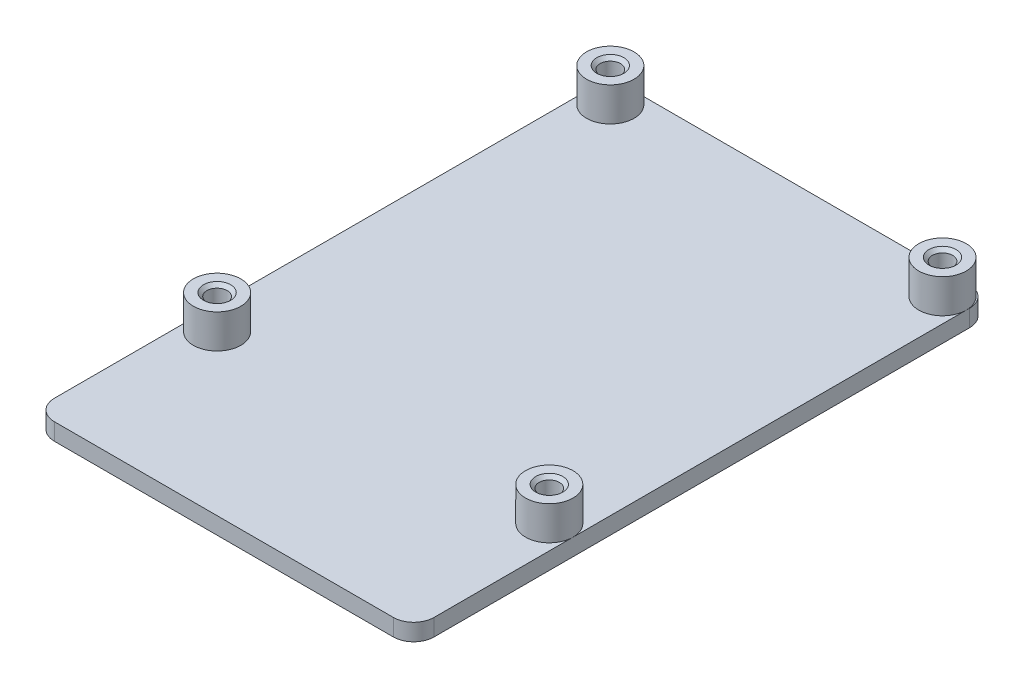
SolidWorks part; units mm, degrees
material "6061-T6 (SS)"
ref_plane "Front Plane" through (0, 0, 0) normal (0, 0, 1) x (1, 0, 0)
ref_plane "Top Plane" through (0, 0, 0) normal (0, 1, 0) x (1, 0, 0)
ref_plane "Right Plane" through (0, 0, 0) normal (1, 0, 0) x (0, 0, -1)
ref_axis "Axis1" through (0, 0, 55) along (0, 0, -1)
sketch "Sketch1" plane through (0, 0, 0) normal (0, 1, 0) x (1, 0, 0)
  line L0 (-125, 0) -> (0, 0) construction
  line L1 (125, 0) -> (125, 125) construction
  line L2 (125, 125) -> (-125, 125) construction
  line L3 (-125, 125) -> (-125, 0) construction
  line L4 (41.25, 3.75) -> (41.25, 1.5) construction
  line L5 (39, 101.5) -> (109, 101.5)
  line L6 (39, 101.5) -> (39, 1.5)
  line L7 (39, 1.5) -> (109, 1.5)
  line L8 (109, 101.5) -> (109, 1.5)
  line L9 (39, 101.5) -> (109, 1.5) construction
  line L10 (39, 1.5) -> (109, 101.5) construction
  line L11 (41.25, 3.75) -> (39, 3.75) construction
  line L12 (-114.29, 77.51) -> (-116.54, 77.51) construction
  line L13 (78.2, 11.5) -> (87.2, 11.5)
  line L14 (78.2, 11.5) -> (78.2, 1.5)
  line L15 (78.2, 1.5) -> (87.2, 1.5)
  line L16 (87.2, 11.5) -> (87.2, 1.5)
  line L17 (78.2, 11.5) -> (87.2, 1.5) construction
  line L18 (78.2, 1.5) -> (87.2, 11.5) construction
  line L19 (90.5, 16.5) -> (106.5, 16.5)
  line L20 (90.5, 16.5) -> (90.5, 1.5)
  line L21 (90.5, 1.5) -> (106.5, 1.5)
  line L22 (106.5, 16.5) -> (106.5, 1.5)
  line L23 (90.5, 16.5) -> (106.5, 1.5) construction
  line L24 (90.5, 1.5) -> (106.5, 16.5) construction
  line L25 (-116.54, 113.59) -> (-93.46, 113.59)
  line L26 (-116.54, 113.59) -> (-116.54, 71.41)
  line L27 (-116.54, 71.41) -> (-93.46, 71.41)
  line L28 (-93.46, 113.59) -> (-93.46, 71.41)
  line L29 (-116.54, 113.59) -> (-93.46, 71.41) construction
  line L30 (-116.54, 71.41) -> (-93.46, 113.59) construction
  line L31 (-114.29, 77.51) -> (-114.29, 71.41) construction
  line L32 (-95.71, 107.49) -> (-95.71, 113.59) construction
  line L33 (-95.71, 107.49) -> (-93.46, 107.49) construction
  line L34 (-64.5, 85.45) -> (-68, 85.45) construction
  line L35 (-65, 88.95) -> (-15, 88.95)
  line L36 (-68, 85.95) -> (-68, 6.95)
  line L37 (-65, 3.95) -> (-15, 3.95)
  line L38 (-12, 85.95) -> (-12, 6.95)
  line L39 (-68, 88.95) -> (-12, 3.95) construction
  line L40 (-68, 3.95) -> (-12, 88.95) construction
  line L41 (-64.5, 85.45) -> (-15.5, 85.45) construction
  line L42 (-64.5, 85.45) -> (-64.5, 27.45) construction
  line L43 (-64.5, 27.45) -> (-15.5, 27.45) construction
  line L44 (-15.5, 85.45) -> (-15.5, 27.45) construction
  line L45 (0, 0) -> (0, 125) construction
  line L46 (0, 0) -> (125, 0) construction
  line L47 (-64.5, 85.45) -> (-64.5, 88.95) construction
  line L48 (74, 0) -> (74, 125) construction
  line L49 (-65.69, 22.9) -> (-49.81, 22.9)
  line L50 (-65.69, 22.9) -> (-65.69, 1.5)
  line L51 (-65.69, 1.5) -> (-49.81, 1.5)
  line L52 (-49.81, 22.9) -> (-49.81, 1.5)
  line L53 (-65.69, 22.9) -> (-49.81, 1.5) construction
  line L54 (-65.69, 1.5) -> (-49.81, 22.9) construction
  line L55 (-45.65, 19.42) -> (-32.35, 19.42)
  line L56 (-45.65, 19.42) -> (-45.65, 1.5)
  line L57 (-45.65, 1.5) -> (-32.35, 1.5)
  line L58 (-32.35, 19.42) -> (-32.35, 1.5)
  line L59 (-45.65, 19.42) -> (-32.35, 1.5) construction
  line L60 (-45.65, 1.5) -> (-32.35, 19.42) construction
  line L61 (-27.65, 19.42) -> (-14.35, 19.42)
  line L62 (-27.65, 19.42) -> (-27.65, 1.5)
  line L63 (-27.65, 1.5) -> (-14.35, 1.5)
  line L64 (-14.35, 19.42) -> (-14.35, 1.5)
  line L65 (-27.65, 19.42) -> (-14.35, 1.5) construction
  line L66 (-27.65, 1.5) -> (-14.35, 19.42) construction
  line L67 (-40, 0) -> (-40, 125) construction
  line L68 (-114.29, 11.41) -> (-114.29, 17.51) construction
  line L69 (-116.54, 53.59) -> (-93.46, 53.59)
  line L70 (-116.54, 53.59) -> (-116.54, 11.41)
  line L71 (-116.54, 11.41) -> (-93.46, 11.41)
  line L72 (-93.46, 53.59) -> (-93.46, 11.41)
  line L73 (-116.54, 53.59) -> (-93.46, 11.41) construction
  line L74 (-116.54, 11.41) -> (-93.46, 53.59) construction
  line L75 (-114.29, 17.51) -> (-116.54, 17.51) construction
  line L76 (-95.71, 53.59) -> (-95.71, 47.49) construction
  line L77 (-95.71, 47.49) -> (-93.46, 47.49) construction
  line L78 (-105, 0) -> (-105, 32.5) construction
  line L79 (-105, 32.5) -> (-105, 92.5) construction
  line L80 (-105, 92.5) -> (-105, 125) construction
  line L81 (-64.5, 27.45) -> (-15.5, 85.45) construction
  line L82 (-15.5, 27.45) -> (-64.5, 85.45) construction
  circle A0 centre (106, 81.5) radius 1.75
  circle A1 centre (106, 19.5) radius 1.75
  circle A2 centre (71.1, 99.7) radius 1.75
  circle A3 centre (68.3, 67.9) radius 1.75
  circle A4 centre (41.25, 3.75) radius 1.75
  circle A5 centre (-95.71, 107.49) radius 1.4
  circle A6 centre (-114.29, 77.51) radius 1.4
  arc A7 (-15, 3.95) -> (-12, 6.95) centre (-15, 6.95) ccw
  arc A8 (-68, 6.95) -> (-65, 3.95) centre (-65, 6.95) ccw
  arc A9 (-15, 88.95) -> (-12, 85.95) centre (-15, 85.95) cw
  arc A10 (-65, 88.95) -> (-68, 85.95) centre (-65, 85.95) ccw
  circle A11 centre (-64.5, 85.45) radius 1.375
  circle A12 centre (-15.5, 85.45) radius 1.375
  circle A13 centre (-64.5, 27.45) radius 1.375
  circle A14 centre (-15.5, 27.45) radius 1.375
  circle A15 centre (-95.71, 47.49) radius 1.4
  circle A16 centre (-114.29, 17.51) radius 1.4
  circle A17 centre (41.25, 3.75) radius 2.84
  point P0 (74, 51.5)
  point P3 (-105, 92.5)
  point P4 (0, 0)
  point P24 (82.7, 6.5)
  point P30 (98.5, 9)
  point P47 (-40, 46.45)
  point P65 (-39, 10.46)
  point P69 (-57.75, 12.2)
  point P84 (-21, 10.46)
  point P89 (-105, 32.5)
  point P111 (-40, 56.45)
  dimension "D5" = 3.5
  dimension "D26" = 3
  dimension "D27" = 2.75
  dimension "D44" = 2.8
  dimension "D49" = 5.68
  dimension "D1" = 250
  dimension "D2" = 125
  dimension "D3" = 100
  dimension "D4" = 70
  dimension "D6" = 20
  dimension "D7" = 3
  dimension "D8" = 82
  dimension "D9" = 1.8
  dimension "D10" = 37.9
  dimension "D11" = 33.6
  dimension "D12" = 40.7
  dimension "D13" = 2.25
  dimension "D14" = 9
  dimension "D15" = 10
  dimension "D16" = 26.3
  dimension "D17" = 16
  dimension "D18" = 15
  dimension "D19" = 10.5
  dimension "D20" = 23.08
  dimension "D21" = 42.18
  dimension "D22" = 6.1
  dimension "D23" = 2.25
  dimension "D24" = 85
  dimension "D25" = 56
  dimension "D28" = 58
  dimension "D29" = 49
  dimension "D30" = 10.25
  dimension "D31" = 29
  dimension "D32" = 47
  dimension "D33" = 21.4
  dimension "D34" = 15.88
  dimension "D35" = 2.45
  dimension "D36" = 13.3
  dimension "D37" = 17.92
  dimension "D38" = 2.45
  dimension "D39" = 2.45
  dimension "D40" = 2.25
  dimension "D41" = 1.5
  dimension "D42" = 40
  dimension "D43" = 1.5
  dimension "D45" = 60
  dimension "D46" = 3.5
  dimension "D47" = 20
  dimension "D48" = 16
sketch "Sketch2" plane through (0, 0, 0) normal (0, 1, 0) x (1, 0, 0)
  line L0 (-68, 85.95) -> (-68, 6.95) construction
  line L1 (-65, 3.95) -> (-15, 3.95) construction
  line L2 (-12, 85.95) -> (-12, 6.95) construction
  line L3 (-65, 88.95) -> (-15, 88.95) construction
  line L4 (-68, 85.95) -> (-68, 6.95)
  line L5 (-65, 3.95) -> (-15, 3.95)
  line L6 (-12, 85.95) -> (-12, 6.95)
  line L7 (-65, 88.95) -> (-15, 88.95)
  arc A0 (-68, 6.95) -> (-65, 3.95) centre (-65, 6.95) ccw construction
  arc A1 (-15, 3.95) -> (-12, 6.95) centre (-15, 6.95) ccw construction
  arc A2 (-12, 85.95) -> (-15, 88.95) centre (-15, 85.95) ccw construction
  arc A3 (-65, 88.95) -> (-68, 85.95) centre (-65, 85.95) ccw construction
  arc A4 (-68, 6.95) -> (-65, 3.95) centre (-65, 6.95) ccw
  arc A5 (-15, 3.95) -> (-12, 6.95) centre (-15, 6.95) ccw
  arc A6 (-12, 85.95) -> (-15, 88.95) centre (-15, 85.95) ccw
  arc A7 (-65, 88.95) -> (-68, 85.95) centre (-65, 85.95) ccw
extrude "Boss-Extrude1" add sketch "Sketch2" along normal blind 2.5
sketch "Sketch3" plane through (0, 2.5, 0) normal (0, 1, 0) x (1, 0, 0)
  circle A8 centre (-64.5, 85.45) radius 1.5
  circle A9 centre (-15.5, 85.45) radius 1.5
  circle A10 centre (-15.5, 27.45) radius 1.5
  circle A11 centre (-64.5, 27.45) radius 1.5
  circle A12 centre (-64.5, 85.45) radius 3.5
  circle A13 centre (-15.5, 85.45) radius 3.5
  circle A14 centre (-15.5, 27.45) radius 3.5
  circle A15 centre (-64.5, 27.45) radius 3.5
  dimension "D1" = 3
  dimension "D2" = 2
extrude "Boss-Extrude2" add sketch "Sketch3" along normal blind 5
chamfer "Chamfer1" distance 0.5 angle 45 4 edges at (-64.5, 7.5, -25.95) (-15.5, 7.5, -25.95) (-15.5, 7.5, -83.95) (-64.5, 7.5, -83.95)
equation "\"D16@Sketch1\"=22.8+3.5"
equation "\"D19@Sketch1\"=7+3.5"
